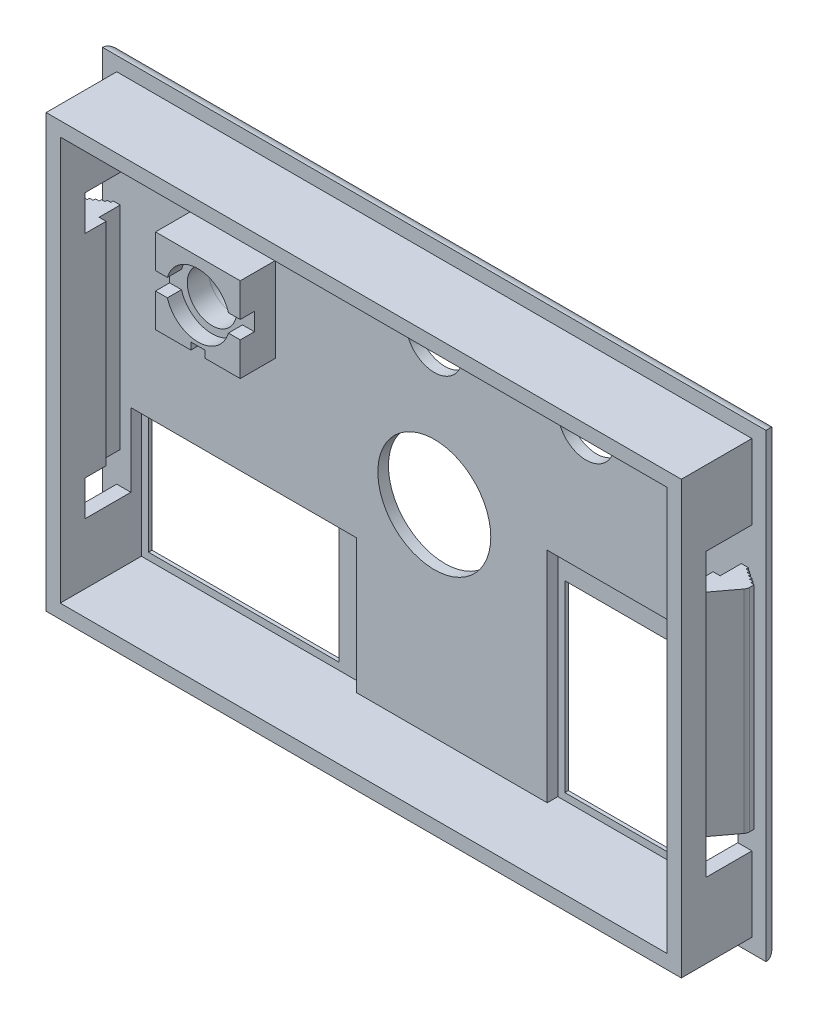
SolidWorks part; units mm, degrees
ref_plane "前视基准面" through (0, 0, 0) normal (0, 0, 1) x (1, 0, 0)
ref_plane "上视基准面" through (0, 0, 0) normal (0, 1, 0) x (1, 0, 0)
ref_plane "右视基准面" through (0, 0, 0) normal (1, 0, 0) x (0, 0, -1)
sketch "草图1" plane through (0, 0, 0) normal (0, 0, 1) x (1, 0, 0)
  line L1 (-47, 32.6) -> (47, 32.6)
  line L2 (-47, 32.6) -> (-47, -32.6)
  line L3 (-47, -32.6) -> (47, -32.6)
  line L4 (47, 32.6) -> (47, -32.6)
  line L5 (-47, 32.6) -> (47, -32.6) construction
  line L6 (-47, -32.6) -> (47, 32.6) construction
  point P0 (0, 0)
  dimension "D1" = 94
  dimension "D2" = 65.2
extrude "凸台-拉伸1" add sketch "草图1" along normal blind 2 contours L3 L4 L1 L2
sketch "草图2" plane through (0, 0, 2) normal (0, 0, 1) x (1, 0, 0)
  line L0 (-15, -27.6) -> (-42, -10.6) construction
  line L1 (-15, -27.6) -> (-42, -27.6)
  line L2 (-15, -27.6) -> (-15, -10.6)
  line L3 (-15, -10.6) -> (-42, -10.6)
  line L4 (-42, -27.6) -> (-42, -10.6)
  line L5 (42, -27.6) -> (17, -27.6)
  line L6 (42, -27.6) -> (42, -1.6)
  line L7 (42, -1.6) -> (17, -1.6)
  line L8 (17, -27.6) -> (17, -1.6)
  line L9 (-15, -10.6) -> (-42, -27.6) construction
  line L10 (42, -27.6) -> (17, -1.6) construction
  line L11 (42, -1.6) -> (17, -27.6) construction
  circle A0 centre (0, 0) radius 8
  circle A1 centre (-28.5, 12.7) radius 3.5
  circle A2 centre (37.5, 20.2) radius 4
  circle A3 centre (21.5, 20.2) radius 4
  circle A4 centre (0, 20.2) radius 4
  point P14 (-28.5, -19.1)
  point P24 (29.5, -14.6)
  dimension "D5" = 16
  dimension "D6" = 7
  dimension "D8" = 8
  dimension "D11" = 8
  dimension "D15" = 8
  dimension "D16" = 8
  dimension "D1" = 17
  dimension "D2" = 27
  dimension "D3" = 26
  dimension "D4" = 25
  dimension "D7" = 19.1
  dimension "D9" = 28.5
  dimension "D10" = 29.5
  dimension "D12" = 20.2
  dimension "D13" = 8
  dimension "D17" = 12.7
extrude "切除-拉伸1" cut sketch "草图2" against normal blind 2
sketch "草图3" plane through (0, 0, 2) normal (0, 0, 1) x (1, 0, 0)
  line L1 (43, -28.6) -> (-43, -28.6)
  line L2 (43, -28.6) -> (43, 28.6)
  line L3 (43, 28.6) -> (-43, 28.6)
  line L4 (-43, -28.6) -> (-43, 28.6)
  line L5 (45, -30.6) -> (-45, -30.6)
  line L6 (45, -30.6) -> (45, 30.6)
  line L7 (45, 30.6) -> (-45, 30.6)
  line L8 (-45, -30.6) -> (-45, 30.6)
  dimension "D1" = 2
  dimension "D2" = 2
  dimension "D3" = 2
  dimension "D4" = 2
  dimension "D5" = 43
  dimension "D6" = 28.6
  dimension "D7" = 28.6
  dimension "D8" = 43
extrude "凸台-拉伸2" add sketch "草图3" along normal blind 10 contours L6 L7 L8 L5 | L2 L3 L4 L1
sketch "草图4" plane through (0, 0, 0) normal (0, 0, -1) x (-1, 0, 0)
  circle A1 centre (0, 0) radius 9
  circle A2 centre (0, 20.2) radius 5
  circle A3 centre (-21.5, 20.2) radius 5
  circle A4 centre (-37.5, 20.2) radius 5
  dimension "D2" = 18
  dimension "D11" = 10
  dimension "D12" = 10
  dimension "D13" = 10
extrude "切除-拉伸4" cut sketch "草图4" against normal blind 0.5
sketch "草图5" plane through (0, 0, 2) normal (0, 0, 1) x (1, 0, 0)
  line L0 (17, -27.6) -> (42, -27.6) construction
  line L1 (43, -28.6) -> (16, -28.6)
  line L2 (43, -28.6) -> (43, 2.4)
  line L3 (43, 2.4) -> (16, 2.4)
  line L4 (16, -28.6) -> (16, 2.4)
  line L5 (42, -27.6) -> (42, -1.6) construction
  line L6 (17, -1.6) -> (17, -27.6) construction
  line L7 (42, -1.6) -> (17, -1.6) construction
  line L8 (-42, -27.6) -> (-15, -27.6) construction
  line L9 (-11, -28.6) -> (-43, -28.6)
  line L10 (-11, -28.6) -> (-11, -9.6)
  line L11 (-11, -9.6) -> (-43, -9.6)
  line L12 (-43, -28.6) -> (-43, -9.6)
  line L14 (-42, -10.6) -> (-42, -27.6) construction
  line L15 (-15, -10.6) -> (-42, -10.6) construction
  line L16 (-15, -27.6) -> (-15, -10.6) construction
  dimension "D1" = 1
  dimension "D2" = 1
  dimension "D3" = 1
  dimension "D4" = 4
  dimension "D5" = 1
  dimension "D6" = 1
  dimension "D7" = 1
  dimension "D8" = 4
extrude "切除-拉伸5" cut sketch "草图5" against normal blind 1.5
sketch "草图6" plane through (0, 0, 2) normal (0, 0, 1) x (1, 0, 0)
  line L0 (-28.5, 9.2) -> (-28.5, 16.2) construction
  line L6 (-22.5, 6.7) -> (-34.5, 6.7)
  line L7 (-22.5, 6.7) -> (-22.5, 18.7)
  line L8 (-22.5, 18.7) -> (-34.5, 18.7)
  line L9 (-34.5, 6.7) -> (-34.5, 18.7)
  line L10 (-22.5, 6.7) -> (-34.5, 18.7) construction
  line L11 (-22.5, 18.7) -> (-34.5, 6.7) construction
  circle A0 centre (-28.5, 12.7) radius 3.5 construction
  point P0 (-28.5, 12.7)
  circle M18 centre (-28.5, 12.7) radius 3.5
  dimension "D1" = 12
  dimension "D2" = 12
extrude "凸台-拉伸4" add sketch "草图6" along normal blind 5 separate body contours L9 L6 L7 L8 M18 region at (-28.5, 6.8697, 2)
sketch "草图7" plane through (0, 0, 7) normal (0, 0, 1) x (1, 0, 0)
  line L0 (-28.5, 9.2) -> (-28.5, 4.2907) construction
  line L1 (-22.5, 6.7) -> (-34.5, 6.7) construction
  line L2 (-27.5, 6.7) -> (-29.5, 6.7)
  line L3 (-27.5, 6.7) -> (-27.5, 7.7)
  line L4 (-27.5, 7.7) -> (-29.5, 7.7)
  line L5 (-29.5, 6.7) -> (-29.5, 7.7)
  circle A0 centre (-28.5, 12.7) radius 3.5 construction
  dimension "D1" = 2
  dimension "D3" = 1
extrude "切除-拉伸6" cut sketch "草图7" against normal blind 3
sketch "草图9" plane through (45, 0, 0) normal (1, 0, 0) x (0, 0, -1)
  line L0 (-8.5, 20) -> (-8.5, 15)
  line L1 (-8.5, 15) -> (-2.5, 15)
  line L2 (-2.5, 15) -> (-2.5, -15)
  line L3 (-2.5, -15) -> (-8.5, -15)
  line L4 (-8.5, -15) -> (-8.5, -20)
  line L5 (-8.5, -20) -> (-4.5187, -20)
  line L6 (-4.5187, -20) -> (-2, -20)
  line L7 (-2, -20) -> (-2, 20)
  line L8 (-2, 20) -> (-8.5, 20)
  line L9 (-2, -30.6) -> (-2, 30.6) construction
  line L10 (-20.086, 0) -> (-0.5045, 0) construction
  point P13 (-8.5, -17.5)
  point P14 (-8.5, 17.5)
  dimension "D1" = 30
  dimension "D2" = 40
  dimension "D4" = 0.5
  dimension "D5" = 6
  dimension "D6" = 6
extrude "切除-拉伸7" cut sketch "草图9" against normal up to next (2 mm away)
sketch "草图10" plane through (45, 0, 0) normal (1, 0, 0) x (0, 0, -1)
  line L1 (-8.5, 15) -> (-2.5, 15)
  line L2 (-8.5, 15) -> (-8.5, -15)
  line L3 (-8.5, -15) -> (-2.5, -15)
  line L4 (-2.5, 15) -> (-2.5, -15)
extrude "凸台-拉伸5" add sketch "草图10" along normal blind 3
sketch "草图13" plane through (0, 15, 0) normal (0, 1, 0) x (1, 0, 0)
  line L1 (48, -2.5) -> (48, -8.5) construction
  line L2 (48, -4.5) -> (48, -2.5)
  line L3 (43, -2.5) -> (48, -2.5) construction
  line L6 (48, -4.5) -> (47.5, -4.5)
  line L7 (47.5, -4.5) -> (47.5, -4.1693)
  line L8 (47.5, -4.1693) -> (47, -4.1693)
  line L9 (47, -4.1693) -> (47, -3.84)
  line L10 (47, -3.84) -> (46.5, -3.84)
  line L11 (46.5, -3.84) -> (46.5, -3.503)
  line L12 (46.5, -3.503) -> (46, -3.503)
  line L13 (46, -3.503) -> (46, -3.1684)
  line L14 (46, -3.1684) -> (45.5, -3.1684)
  line L15 (45.5, -3.1684) -> (45.5, -2.8377)
  line L16 (45.5, -2.8377) -> (45, -2.8377)
  line L17 (45, -2.8377) -> (45, -2.5)
  line L18 (48, -2.5) -> (45, -2.5)
  point P19 (47.25, -4.1693)
  dimension "D1" = 0.5
  dimension "D2" = 0.5
  dimension "D3" = 0.5
  dimension "D4" = 0.5
  dimension "D5" = 0.5
  dimension "D6" = 0.5
  dimension "D7" = 2
  dimension "D8" = 1.6693
  dimension "D9" = 1.34
  dimension "D10" = 1.003
  dimension "D11" = 0.6684
  dimension "D12" = 0.3377
extrude "切除-拉伸9" cut sketch "草图13" against normal up to next (30 mm away)
sketch "草图14" plane through (0, 15, 0) normal (0, 1, 0) x (1, 0, 0)
  line L0 (45, -8.5) -> (48, -4.5)
  line L1 (48, -4.5) -> (48, -8.5)
  line L2 (48, -8.5) -> (45, -8.5)
extrude "切除-拉伸10" cut sketch "草图14" against normal up to next (30 mm away)
sketch "草图15" plane through (0, 15, 0) normal (0, 1, 0) x (1, 0, 0)
  line L0 (47.5, -4.5) -> (47.5, -5.1667)
  line L1 (48, -4.5) -> (45, -8.5) construction
  line L2 (47.5, -5.1667) -> (48, -4.5)
  line L3 (48, -4.5) -> (47.5, -4.5)
extrude "切除-拉伸11" cut sketch "草图15" against normal up to next (30 mm away)
fillet "圆角1" radius 1 1 edges at (47.5, 0, 5.1667)
ref_plane "基准面1" through (0, 0, 0) normal (0, -1, 0) x (-1, 0, 0)
ref_plane "基准面2" through (0, 0, 0) normal (1, 0, 0) x (0, 0, -1)
fillet "圆角2" radius 2 4 edges at (47, 0, 0) (0, -32.6, 0) (-47, 0, 0) (0, 32.6, 0)
mirror "镜向9" about plane through (0, 0, 0) normal (1, 0, 0) of "凸台-拉伸5", "切除-拉伸9", "切除-拉伸11", "切除-拉伸10", "圆角1", "切除-拉伸7"
sketch "草图17" plane through (0, 0, 7) normal (0, 0, 1) x (1, 0, 0)
  circle A0 centre (-28.5, 12.7) radius 4.5
  circle A1 centre (-28.5, 12.7) radius 3.5 construction
  dimension "D1" = 9
extrude "切除-拉伸13" cut sketch "草图17" against normal blind 2
sketch "草图18" plane through (0, 0, 7) normal (0, 0, 1) x (1, 0, 0)
  line L0 (-34.5, 6.7) -> (-34.5, 18.7) construction
  line L1 (-34.5, 11.45) -> (-32.8229, 11.45)
  line L2 (-34.5, 11.45) -> (-34.5, 13.95)
  line L3 (-34.5, 13.95) -> (-32.8229, 13.95)
  line L4 (-32.8229, 11.45) -> (-32.8229, 13.95)
  line L5 (-22.5, 12.7) -> (-37.3749, 12.7) construction
  line L6 (-22.5, 6.7) -> (-22.5, 18.7) construction
  circle A0 centre (-28.5, 12.7) radius 4.5 construction
  dimension "D1" = 2.5
extrude "切除-拉伸14" cut sketch "草图18" against normal blind 2
ref_plane "基准面3" through (-28.5, 0, 0) normal (1, 0, 0) x (0, 0, -1)
mirror "镜向10" about plane through (-28.5, 0, 0) normal (1, 0, 0) of "切除-拉伸14"
sketch "草图19" plane through (0, 15, 0) normal (0, 1, 0) x (1, 0, 0)
  line L0 (43, -2.5) -> (45, -2.5) construction
  line L1 (43, -2.5) -> (44, -2.5)
  line L2 (43, -2.5) -> (43, -5.5)
  line L3 (43, -5.5) -> (44, -5.5)
  line L4 (44, -2.5) -> (44, -5.5)
  dimension "D1" = 1
  dimension "D2" = 3
extrude "切除-拉伸15" cut sketch "草图19" against normal up to next (30 mm away)
mirror "镜向11" about plane through (0, 0, 0) normal (1, 0, 0) of "切除-拉伸15"
